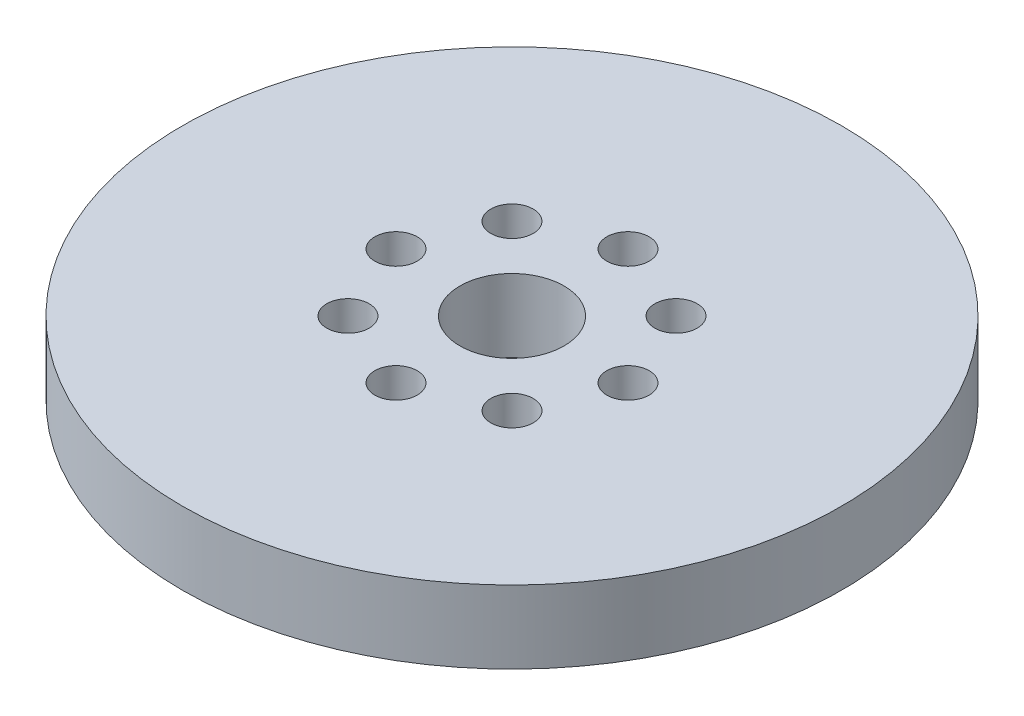
SolidWorks part; units mm, degrees
ref_plane "Front Plane" through (0, 0, 0) normal (0, 0, 1) x (1, 0, 0)
ref_plane "Top Plane" through (0, 0, 0) normal (0, 1, 0) x (1, 0, 0)
ref_plane "Right Plane" through (0, 0, 0) normal (1, 0, 0) x (0, 0, -1)
sketch "Sketch1" plane through (0, 0, 0) normal (0, 1, 0) x (1, 0, 0)
  circle A0 centre (0, 0) radius 95
  dimension "FLANGE_OD" = 190
extrude "Boss-Extrude1" add sketch "Sketch1" along normal blind 21
sketch "Sketch2" plane through (0, 0, 0) normal (0, 1, 0) x (1, 0, 0)
  circle A0 centre (0, 0) radius 15
  dimension "BORE_D" = 30
extrude "Cut-Extrude1" cut sketch "Sketch2" along normal through all
sketch "Sketch3" plane through (0, 21, 0) normal (0, 1, 0) x (1, 0, 0)
  circle A0 centre (0, 0) radius 33.4353 construction
  circle A1 centre (-33.4353, 0) radius 6.1116
  dimension "BOLT_D" = 12.2232
  dimension "BOLT_PCD" = 66.8705
extrude "Cut-Extrude2" cut sketch "Sketch3" against normal blind 14.6395
pattern_circular "CirPattern1" count 8 over 360 about axis through (0, 0, 0) along (0, 1, 0) of "Cut-Extrude2"
